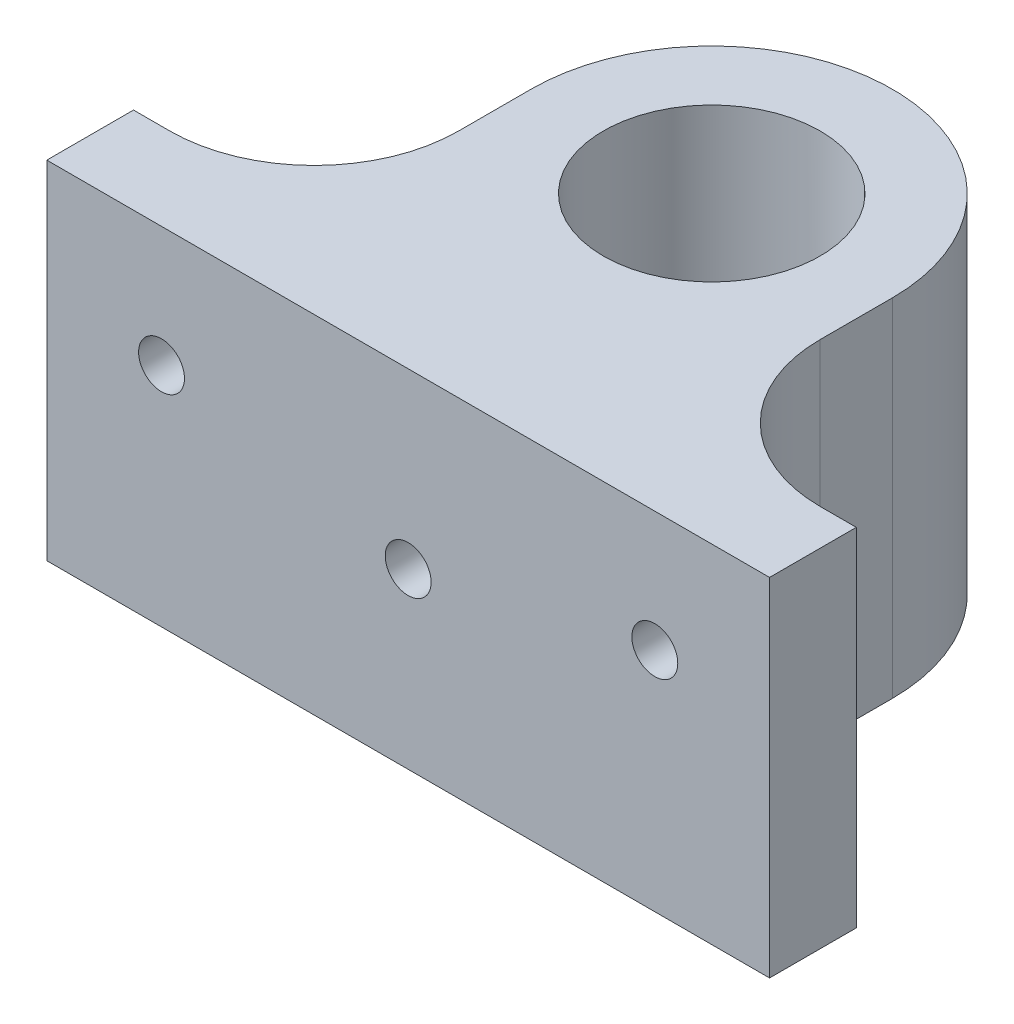
SolidWorks part; units mm, degrees
ref_plane "Front Plane" through (0, 0, 0) normal (0, 0, 1) x (1, 0, 0)
ref_plane "Top Plane" through (0, 0, 0) normal (0, 1, 0) x (1, 0, 0)
ref_plane "Right Plane" through (0, 0, 0) normal (1, 0, 0) x (0, 0, -1)
sketch "Profile-Sketch1" plane through (0, 0, 0) normal (0, 1, 0) x (1, 0, 0)
  line L0 (-25, -21) -> (25, -21)
  line L1 (25, -21) -> (25, -15)
  line L2 (-25, -21) -> (-25, -15)
  line L3 (-25, -15) -> (-22.5, -15)
  line L4 (-12.5, -5) -> (-12.5, 0)
  line L5 (25, -15) -> (22.5, -15)
  line L6 (12.5, -5) -> (12.5, 0)
  circle A0 centre (0, 0) radius 7.5
  arc A6 (12.5, 0) -> (-12.5, 0) centre (0, 0) ccw
  arc A7 (22.5, -15) -> (12.5, -5) centre (22.5, -5) cw
  arc A8 (-12.5, -5) -> (-22.5, -15) centre (-22.5, -5) cw
  dimension "D1" = 15
  dimension "D2" = 12.5
  dimension "D7" = 10
  dimension "D3" = 50
  dimension "D4" = 25
  dimension "D5" = 21
  dimension "D6" = 6
extrude "Profile-Boss-Extrude2" add sketch "Profile-Sketch1" along normal blind 24
sketch "FasteningHoleSketch3" plane through (0, 0, 21) normal (0, 0, 1) x (1, 0, 0)
  line L0 (25, 24) -> (25, 0) construction
  line L1 (-25, 24) -> (-25, 0) construction
  line L2 (-25, 0) -> (25, 0) construction
  circle A2 centre (-17.0625, 15.6776) radius 1.5875
  circle A3 centre (17.0625, 15.6776) radius 1.5875
  point P12 (0, 0)
  point P13 (0, 0)
  dimension "D3" = 3.175
  dimension "D6" = 7.9375
  dimension "D2" = 15.6776
  dimension "D1" = 7.9375
extrude "FasteningHoleCut-Extrude8" cut sketch "FasteningHoleSketch3" against normal through all
sketch "LM8UUFasteningHoleSketch5" plane through (0, 0, 21) normal (0, 0, 1) x (1, 0, 0)
  line L0 (25, 24) -> (25, 0) construction
  line L1 (-25, 0) -> (25, 0) construction
  circle A0 centre (0, 12) radius 1.5875
  circle A1 centre (-17.0625, 15.6776) radius 1.5875 construction
  dimension "D1" = 25
  dimension "D2" = 12
extrude "LM8UUFasteningHoleCut-Extrude9" cut sketch "LM8UUFasteningHoleSketch5" against normal through all
equation "\"RailThickness\"= .125in'Spec"
equation "\"LM8UUDiameter\"= 15mm"
equation "\"MidLeftOrRightSideRailHeight\"= 2.0in"
equation "\"RodStabilizerLength\"= 50mm"
equation "\"HoleOffsetFromEdge\"= \"RailThickness\" * 2.5"
equation "\"StepperMountingHoleOffsetFromItsSide\"= 5.5mm'Spec"
equation "\"StepperMountingHoleOffsetFromLeftOrRightSide\"= \"StepperMountingHoleOffsetFromItsSide\" + \"RailThickness\""
equation "\"StepperMountingHoleDistance\"= 31mm'Spec"
equation "\"LM8UUHeight\"= 24mm'Spec"
equation "\"ZAxisLeadScrewLength\"= 200mm"
equation "\"LegHeight\"= 70mm'Space needed for PSU/Stepper/Electronics"
equation "\"V1 BottomOfLowerRail\"= \"LegHeight\""
equation "\"StepperShaftLength\"= 24mm'Pulley will be attached to the end"
equation "\"V2 ToBedAtTopOfZAxis\"= \"V1 BottomOfLowerRail\" - \"LowerEnclosureThickness\" + \"StepperShaftLength\" + \"ZAxisLeadScrewLength\" - \"LM8UUHeight\" / 2"
equation "\"HotEndToTopOfXAxisGB\"= 63.315144mm'Measured from the100.Should be 63.315144"
equation "\"TopOfGBToBottomOfLinearRail\"= \"LinearGBWidth\" / 2 + \"LinearRailWidth\" / 2"
equation "\"LinearGBWidth\"= 27mm'Spec"
equation "\"V5 ToBottomOfXAxisLinearRail\"= \"V4 ToTopOfBuildPlate/HotEndTip\" + \"HotEndToTopOfXAxisGB\" - \"TopOfGBToBottomOfLinearRail\""
equation "\"LinearRailWidth\"= 12mm'Spec"
equation "\"V6 ToBottomOfGantryPulley\"= \"V5 ToBottomOfXAxisLinearRail\" - \"DistanceFromGABTopToLowerPulley\""
equation "\"GABUpperHeight\"= 6mm"
equation "\"GABMidWallHeight\"= 28mm'Must equal 28 or changes alignment"
equation "\"20TGT2PulleyWidth\"= 8.7mm'The STL of the Pulley in the diagram is a bit larger"
equation "\"GABMidShortRiserHeight\"= \"GABMidWallHeight\" / 2 - \"20TGT2PulleyWidth\"'Equals 5.3"
equation "\"GABRiserBossOffset\"= 0.8mm'Aligns Pulleys"
equation "\"DistanceFromGABTopToLowerPulley\"= \"GABUpperHeight\" + \"GABMidWallHeight\" - \"GABMidShortRiserHeight\" + \"GABRiserBossOffset\" / 2"
equation "\"V7 ToTopOfMidBackRail\"= \"V6 ToBottomOfGantryPulley\" + \"StepperShaftLength\""
equation "\"BedToBuildPlateStandoffLength\"= 15mm"
equation "\"BuildPlateHeight\"= 8mm'Spec"
equation "\"V4 ToTopOfBuildPlate/HotEndTip\"= \"V2 ToBedAtTopOfZAxis\" + \"BedToBuildPlateStandoffLength\" + \"BuildPlateHeight\""
equation "\"FasteningHoleDiameter\"= .125in"
equation "\"RodStabilizerHeight\"= \"LM8UUHeight\""
equation "\"LowerEnclosureThickness\"= 5mm"
equation "\"D1@Profile-Sketch1\" = \"LM8UUDiameter\""
equation "\"D3@Profile-Sketch1\" = \"RodStabilizerLength\""
equation "\"D4@Profile-Sketch1\" = \"RodStabilizerLength\" / 2"
equation "\"RodStabilizerWidthFromMidRailToZAxisRodCenter\"= \"StepperMountingHoleOffsetFromLeftOrRightSide\" + \"StepperMountingHoleDistance\" / 2 - \"RailThickness\""
equation "\"StandardWallThickness\"= 3mm"
equation "\"D6@Profile-Sketch1\" = \"StandardWallThickness\" * 2"
equation "\"D1@Profile-Boss-Extrude2\"= \"RodStabilizerHeight\""
equation "\"D6@FasteningHoleSketch3\"=\"HoleOffsetFromEdge\""
equation "\"D2@LM8UUFasteningHoleSketch5\"=\"LM8UUHeight\"/2"
equation "\"V8 ToTopOfMidSideRail\"= \"V7 ToTopOfMidBackRail\" - \"RailThickness\""
equation "\"RodStabilizerMountingHoleOffsetInsideX\"= 14.125mm'Backward compatible"
equation "\"RodStabilizerMountingHoleOffsetOutsideX\"= 12mm"
equation "\"D5@Profile-Sketch1\"=\"RodStabilizerWidthFromMidRailToZAxisRodCenter\""
equation "\"V3 ToTopOfZAxisLM8UU\"= \"V2 ToBedAtTopOfZAxis\" + \"LM8UUHeight\""
equation "\"RodStabilizerMountingHoleYOffsetFromBottom\"= \"RodStabilizerHeight\" - ( \"V3 ToTopOfZAxisLM8UU\" - \"V8 ToTopOfMidSideRail\" + \"MidLeftOrRightSideRailHeight\" ) + \"HoleOffsetFromEdge\""
equation "\"D2@FasteningHoleSketch3\"=\"RodStabilizerMountingHoleYOffsetFromBottom\""
equation "\"D3@FasteningHoleSketch3\"=\"FasteningHoleDiameter\""
